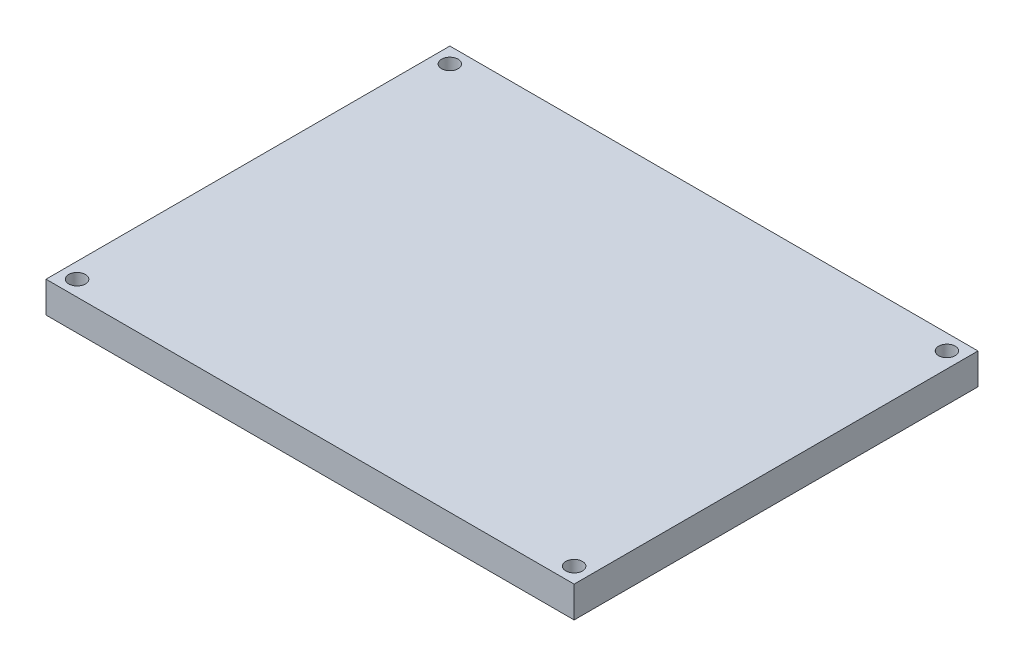
SolidWorks part; units mm, degrees
material "Polyurethane Foam Rigid"
ref_plane "Front Plane" through (0, 0, 0) normal (0, 0, 1) x (1, 0, 0)
ref_plane "Top Plane" through (0, 0, 0) normal (0, 1, 0) x (1, 0, 0)
ref_plane "Right Plane" through (0, 0, 0) normal (1, 0, 0) x (0, 0, -1)
sketch "Sketch1" plane through (0, 0, 0) normal (0, 1, 0) x (1, 0, 0)
  line L0 (-53.975, 41.275) -> (53.975, 41.275)
  line L1 (-50.8, -38.1) -> (50.8, -38.1) construction
  line L2 (-50.8, -38.1) -> (-50.8, 38.1) construction
  line L3 (-50.8, 38.1) -> (50.8, 38.1) construction
  line L4 (50.8, -38.1) -> (50.8, 38.1) construction
  line L5 (-50.8, -38.1) -> (50.8, 38.1) construction
  line L6 (-50.8, 38.1) -> (50.8, -38.1) construction
  line L7 (53.975, -41.275) -> (53.975, 41.275)
  line L8 (-53.975, -41.275) -> (53.975, -41.275)
  line L9 (-53.975, -41.275) -> (-53.975, 41.275)
  point P0 (0, 0)
  dimension "D1" = 101.6
  dimension "D2" = 76.2
  dimension "D3" = 3.175
extrude "Boss-Extrude1" add sketch "Sketch1" along normal blind 6.35
hole_wizard "M3 Clearance Hole1" positions "3DSketch1" profile "Sketch2" hole size "M3" standard "ANSI Metric" end condition through all
sketch3d "3DSketch1"
  point P0 (-50.8, 0, 38.1)
  point P3 (50.8, 0, 38.1)
  point P6 (-50.8, 0, -38.1)
  point P9 (50.8, 0, -38.1)
sketch "Sketch2" plane through (-50.8, 0, 38.1) normal (1, 0, 0) x (0, 0, -1)
  line L0 (0, 0) -> (0, 6.35)
  line L1 (0, 6.35) -> (1.7, 6.35)
  line L2 (1.7, 6.35) -> (1.7, 0)
  line L5 (1.7, 0) -> (0, 0)
  line L11 (0, -6.35) -> (0, 107.95) construction
  dimension "Thru Hole Dia." = 3.4
  dimension "Thru Hole Depth" = 6.35
